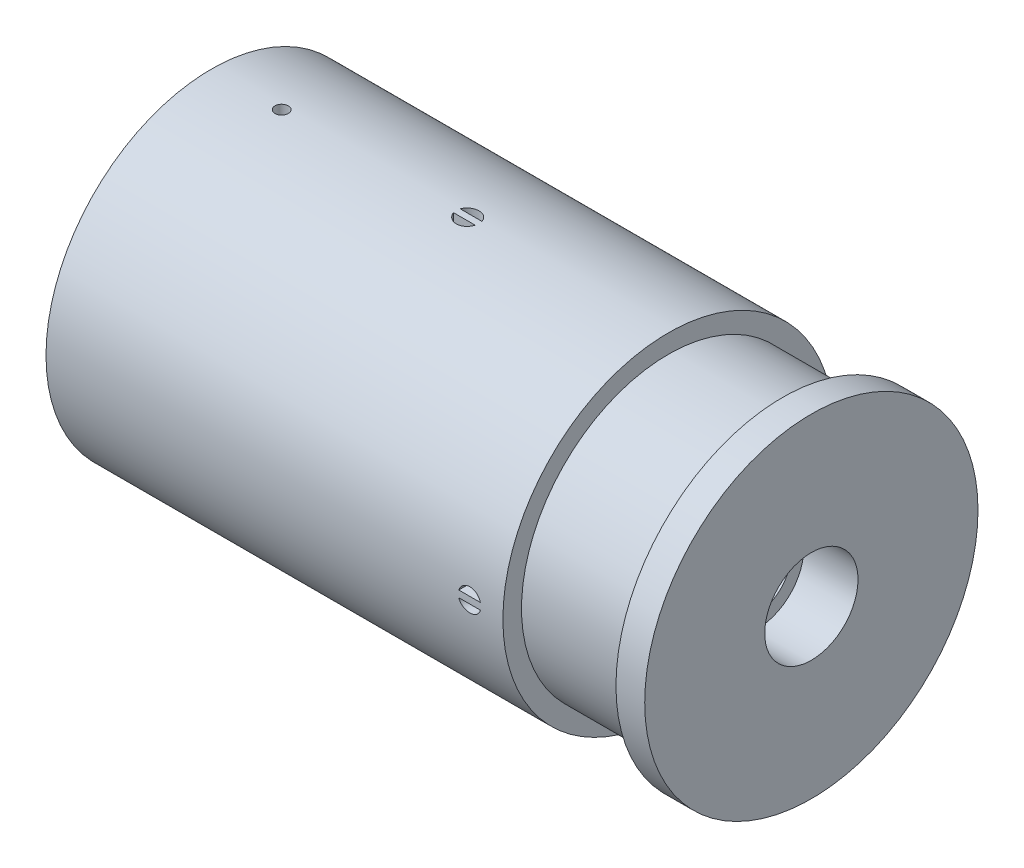
SolidWorks part; units mm, degrees
material "AISI 316 Stainless Steel Sheet (SS)"
ref_plane "Front Plane" through (0, 0, 0) normal (0, 0, 1) x (1, 0, 0)
ref_plane "Top Plane" through (0, 0, 0) normal (0, 1, 0) x (1, 0, 0)
ref_plane "Right Plane" through (0, 0, 0) normal (1, 0, 0) x (0, 0, -1)
sketch "Sketch1" plane through (0, 0, 0) normal (0, 0, 1) x (1, 0, 0)
  line L0 (0, 0) -> (0, 24.8206)
  line L1 (0, 24.8206) -> (68.544, 24.8206)
  line L2 (68.544, 24.8206) -> (68.544, 22.0281)
  line L3 (68.544, 22.0281) -> (85.6845, 22.0281)
  line L4 (85.6845, 22.0281) -> (85.6845, 25)
  line L5 (85.6845, 25) -> (90, 25)
  line L6 (90, 25) -> (90, 0)
  line L7 (90, 0) -> (0, 0)
  line L8 (0, 0) -> (-9.0426, 0) construction
  line L9 (-9.0426, 0) -> (117.8661, 0) construction
  dimension "D1" = 25
  dimension "D2" = 90
revolve "Revolve1" add sketch "Sketch1" angle 360 about L8
sketch "Sketch3" plane through (0, 0, 0) normal (0, 1, 0) x (1, 0, 0)
  line L0 (0, 0) -> (0, 13)
  line L1 (0, 24.8206) -> (0, -24.8206) construction
  line L2 (0, 13) -> (11.1868, 13)
  line L3 (11.1868, 13) -> (11.1868, 11)
  line L4 (11.1868, 11) -> (14.3932, 11)
  line L5 (14.3932, 11) -> (14.3932, 9)
  line L6 (14.3932, 9) -> (69.9226, 9)
  line L7 (69.9226, 9) -> (69.9226, 5)
  line L8 (69.9226, 5) -> (81.8739, 5)
  line L9 (81.8739, 5) -> (81.8739, 7)
  line L10 (81.8739, 7) -> (90, 7)
  line L11 (90, -25) -> (90, 25) construction
  line L12 (90, 7) -> (90, 0)
  line L13 (90, 0) -> (0, 0)
  line L14 (0, 0) -> (96.4485, 0) construction
  line L15 (96.4485, 0) -> (-9.5092, 0) construction
  dimension "D1" = 7
  dimension "D2" = 5
  dimension "D3" = 11
  dimension "9" = 9
  dimension "D4" = 13
revolve "Cut-Revolve1" cut sketch "Sketch3" angle 360 about L15
ref_plane "Plane1" through (0, -25, 0) normal (0, 1, 0) x (1, 0, 0)
sketch "Sketch4" plane through (0, 0, 0) normal (0, 0, 1) x (1, 0, 0)
  line L0 (68.544, 0) -> (38.044, 0) construction
  line L1 (68.544, 0) -> (10.544, 0) construction
  line L2 (68.544, -22.0281) -> (68.544, 22.0281) construction
  line L3 (90, 0) -> (0, 0) construction
  circle A0 centre (38.044, 0) radius 1.7
  point P7 (0, 0)
  dimension "D1" = 58
extrude "Cut-Extrude1" cut sketch "Sketch4" against normal blind 22 and the other way blind 21
sketch "Sketch5" plane through (0, 0, 0) normal (0, 0, 1) x (1, 0, 0)
  line L0 (68.544, 0) -> (10.544, 0) construction
  line L1 (68.544, -22.0281) -> (68.544, 22.0281) construction
  line L2 (90, 0) -> (0, 0) construction
  circle A0 centre (10.544, 0) radius 1
extrude "Cut-Extrude2" cut sketch "Sketch5" against normal blind 21
ref_plane "Plane2" through (0, 25, 0) normal (0, 1, 0) x (1, 0, 0)
sketch "Sketch7" plane through (0, 25, 0) normal (0, 1, 0) x (1, 0, 0)
  line L0 (68.544, 0) -> (38.444, 0) construction
  line L1 (68.544, -24.8206) -> (68.544, 24.8206) construction
  line L2 (36.8192, 0.5) -> (40.0688, 0.5)
  line L3 (36.8192, -0.5) -> (40.0688, -0.5)
  arc A0 (36.8192, -0.5) -> (40.0688, -0.5) centre (38.444, 0) ccw
  arc A1 (40.0688, 0.5) -> (36.8192, 0.5) centre (38.444, 0) ccw
  dimension "D1" = 0.5
  dimension "D3" = 3.4
  dimension "30." = 30.1
  dimension "D2" = 0.5
extrude "Cut-Extrude3" cut sketch "Sketch7" against normal blind 25
ref_plane "Plane3" through (0, 0, 25) normal (0, 0, 1) x (1, 0, 0)
sketch "Sketch8" plane through (0, 0, 25) normal (0, 0, 1) x (1, 0, 0)
  line L0 (68.544, 0) -> (63.544, 0) construction
  line L1 (68.544, -22.0281) -> (68.544, 22.0281) construction
  line L2 (61.9192, 0.5) -> (65.1688, 0.5)
  line L3 (61.9192, -0.5) -> (65.1688, -0.5)
  arc A0 (61.9192, -0.5) -> (65.1688, -0.5) centre (63.544, 0) ccw
  arc A1 (65.1688, 0.5) -> (61.9192, 0.5) centre (63.544, 0) ccw
  dimension "D2" = 3.4
  dimension "D1" = 5
  dimension "D3" = 0.5
  dimension "D4" = 0.5
extrude "Cut-Extrude4" cut sketch "Sketch8" against normal blind 25
sketch "Sketch9" plane through (0, 25, 0) normal (0, 1, 0) x (1, 0, 0)
  line L0 (68.544, 0) -> (10.544, 0)
  line L1 (68.544, -22.0281) -> (68.544, 22.0281) construction
  circle A0 centre (10.544, 0) radius 1
  dimension "D2" = 2
  dimension "D1" = 58
extrude "Cut-Extrude5" cut sketch "Sketch9" against normal blind 25 contours A0
